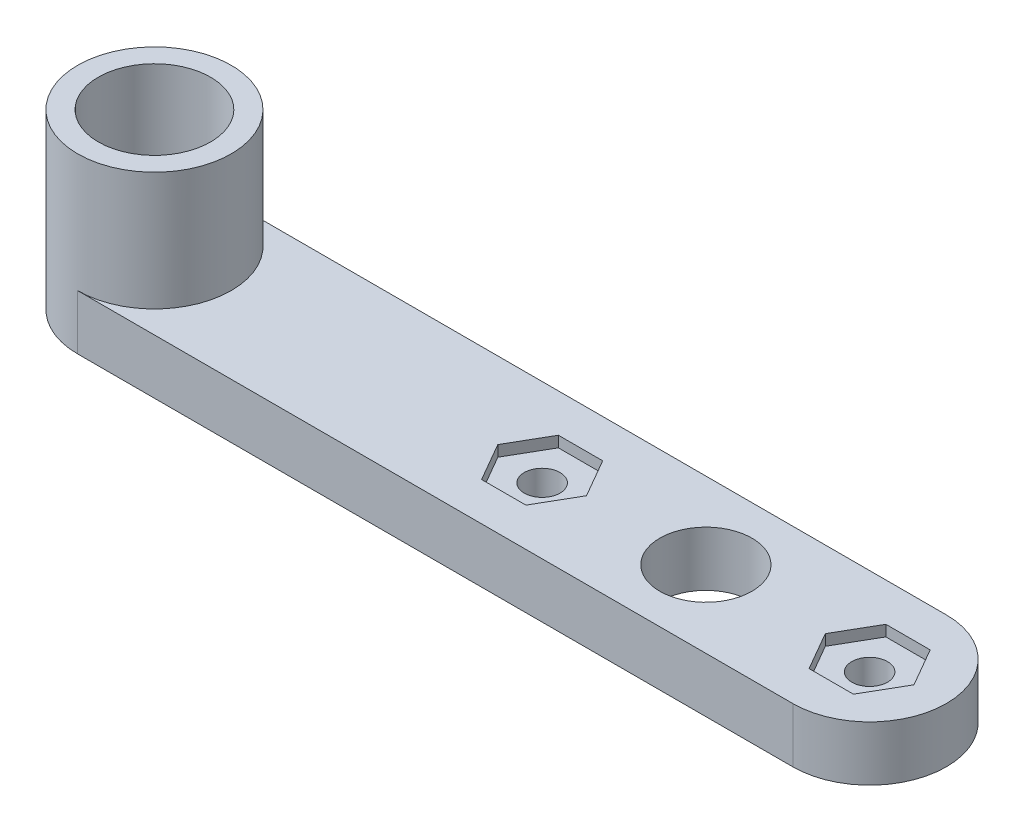
SolidWorks part; units mm, degrees
ref_plane "Front Plane" through (0, 0, 0) normal (0, 0, 1) x (1, 0, 0)
ref_plane "Top Plane" through (0, 0, 0) normal (0, 1, 0) x (1, 0, 0)
ref_plane "Right Plane" through (0, 0, 0) normal (1, 0, 0) x (0, 0, -1)
sketch "Sketch1" plane through (0, 0, 0) normal (0, 1, 0) x (1, 0, 0)
  line L0 (0, 0) -> (82.8167, 0) construction
  line L1 (0, 8.89) -> (82.8167, 8.89)
  line L2 (0, -8.89) -> (82.8167, -8.89)
  line L3 (44.8945, 0) -> (82.8167, 0) construction
  arc A0 (0, 8.89) -> (0, -8.89) centre (0, 0) ccw
  arc A1 (82.8167, -8.89) -> (82.8167, 8.89) centre (82.8167, 0) ccw
  circle A2 centre (0, 0) radius 6.5024
  circle A3 centre (82.8167, 0) radius 2.0701
  circle A4 centre (44.8945, 0) radius 2.0701
  circle A5 centre (63.8556, 0) radius 5.334
  point P3 (41.4084, 0)
  dimension "D1" = 8.89
  dimension "D3" = 13.0048
  dimension "D5" = 4.1402
  dimension "D6" = 10.668
  dimension "D4" = 37.9222
  dimension "D2" = 63.8556
extrude "Boss-Extrude1" add sketch "Sketch1" along normal blind 6.35
sketch "Sketch2" plane through (0, 6.35, 0) normal (0, 1, 0) x (1, 0, 0)
  line L1 (50.0271, 0) -> (47.4608, 4.445)
  line L2 (47.4608, 4.445) -> (42.3282, 4.445)
  line L3 (42.3282, 4.445) -> (39.7619, 0)
  line L4 (39.7619, 0) -> (42.3282, -4.445)
  line L5 (42.3282, -4.445) -> (47.4608, -4.445)
  line L6 (47.4608, -4.445) -> (50.0271, 0)
  line L7 (77.6841, 0) -> (80.2504, -4.445)
  line L8 (80.2504, -4.445) -> (85.383, -4.445)
  line L9 (85.383, -4.445) -> (87.9493, 0)
  line L10 (87.9493, 0) -> (85.383, 4.445)
  line L11 (85.383, 4.445) -> (80.2504, 4.445)
  line L12 (80.2504, 4.445) -> (77.6841, 0)
  circle A2 centre (44.8945, 0) radius 4.445 construction
  circle A3 centre (82.8167, 0) radius 4.445 construction
  dimension "D1" = 8.89
  dimension "D2" = 8.89
extrude "Cut-Extrude1" cut sketch "Sketch2" against normal blind 1.27
sketch "Sketch3" plane through (0, 6.35, 0) normal (0, 1, 0) x (1, 0, 0)
  circle A0 centre (0, 0) radius 8.89
  circle A1 centre (0, 0) radius 6.5024 construction
  circle A2 centre (0, 0) radius 6.5024
extrude "Boss-Extrude2" add sketch "Sketch3" along normal blind 13.716
equation "\"D4@Sketch1\"=1.32+0.173"
equation "\"D2@Sketch1\"=2.233+1/2*0.25+1/2*0.312"
